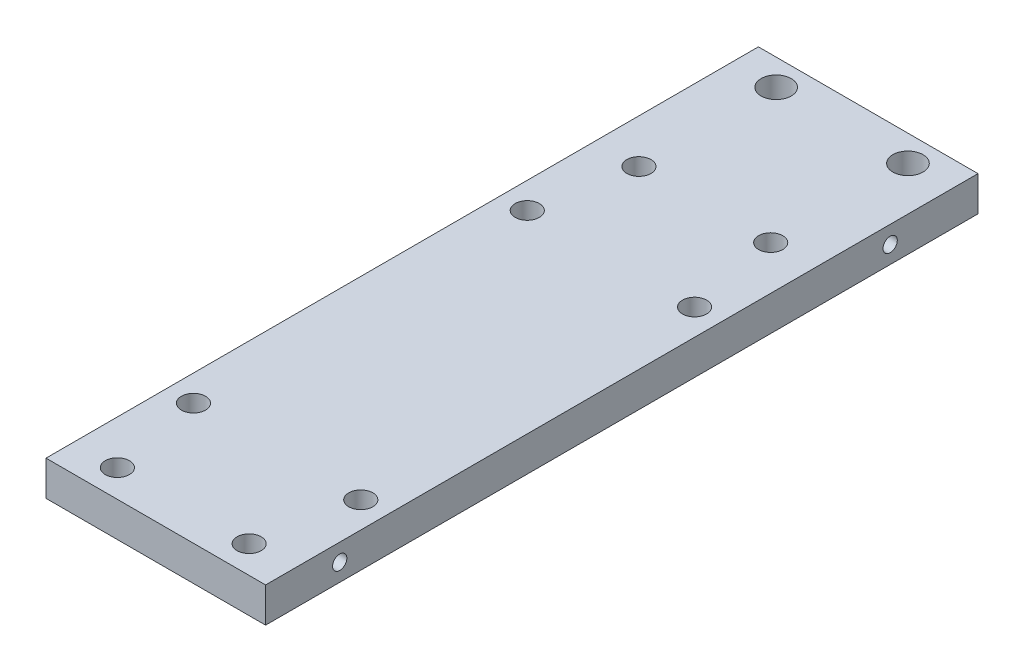
SolidWorks part; units mm, degrees
material "6061 Alloy"
ref_plane "Front Plane" through (0, 0, 0) normal (0, 0, 1) x (1, 0, 0)
ref_plane "Top Plane" through (0, 0, 0) normal (0, 1, 0) x (1, 0, 0)
ref_plane "Right Plane" through (0, 0, 0) normal (1, 0, 0) x (0, 0, -1)
sketch "Sketch1" plane through (0, 0, 0) normal (0, 1, 0) x (1, 0, 0)
  line L1 (-20, 80) -> (20, 80)
  line L2 (-20, 80) -> (-20, -80)
  line L3 (-20, -80) -> (20, -80)
  line L4 (20, 80) -> (20, -80)
  line L5 (0, -80) -> (0, 80) construction
  line L6 (-20, 0) -> (20, 0) construction
  point P0 (0, 0)
  dimension "D1" = 40
  dimension "D2" = 160
extrude "Boss-Extrude1" add sketch "Sketch1" along normal mid plane 6.35
sketch "Sketch3" plane through (0, 0, 0) normal (0, 1, 0) x (1, 0, 0)
  line L0 (0, 75.2375) -> (12, 75.2375) construction
  line L5 (0, -80) -> (0, 80) construction
  line L6 (-20, 0) -> (20, 0) construction
  line L7 (0, 50.2375) -> (12, 50.2375) construction
  line L8 (20, 80) -> (-20, 80) construction
  line L9 (-20, 80) -> (-20, -80) construction
  line L10 (-20, -80) -> (20, -80) construction
  line L11 (20, -80) -> (20, 80) construction
  circle A0 centre (12, 75.2375) radius 2.75
  circle A1 centre (12, 50.2375) radius 2.2
  circle A2 centre (-12, 50.2375) radius 2.2
  circle A3 centre (-12, 75.2375) radius 2.75
  circle A4 centre (-12, -44.7625) radius 2.2
  circle A5 centre (12, -44.7625) radius 2.2
  point P0 (0, 0)
  dimension "D4" = 5.5
  dimension "D5" = 4.4
  dimension "D1" = 4.7625
  dimension "D2" = 25
  dimension "D3" = 12
  dimension "D6" = 2
extrude "M4/5_through" cut sketch "Sketch3" against normal up to surface (3.175 mm away) and the other way blind 6.35 up to face at (0, -3.175, 0)
sketch "Sketch4" plane through (0, 0, -80) normal (0, 0, -1) x (-1, 0, 0)
  circle A0 centre (0, 0) radius 1.35
  dimension "D1" = 2.7
extrude "M3_DRILL" cut sketch "Sketch4" against normal blind 8
sketch "Sketch5" plane through (0, 3.175, 0) normal (0, 1, 0) x (1, 0, 0)
  line L0 (-12, -44.7625) -> (0, -44.7625) construction
  line L2 (0, 0) -> (0, -23.6676) construction
  line L3 (-12, 50.2375) -> (-12, -44.7625) construction
  line L4 (-12, 2.7375) -> (-1.1233, 2.7375) construction
  line L5 (-20, 80) -> (-20, -80) construction
  circle A0 centre (-15.2375, -27.6625) radius 2.2
  circle A1 centre (15.2375, -27.6625) radius 2.2
  circle A2 centre (15.2375, 33.1375) radius 2.2
  circle A3 centre (-15.2375, 33.1375) radius 2.2
  circle A4 centre (-12, -44.7625) radius 2.2 construction
  circle A6 centre (-12, 50.2375) radius 2.2 construction
  dimension "D2" = 4.4
  dimension "D1" = 17.1
  dimension "D3" = 4.7625
extrude "M4_through" cut sketch "Sketch5" against normal up to surface (6.35 mm away) up to face at (12, -3.175, 46.9625)
sketch "Sketch6" plane through (0, 3.175, 0) normal (0, 1, 0) x (1, 0, 0)
  line L0 (-12, -44.7625) -> (12, -44.7625) construction
  line L2 (20, -80) -> (20, 80) construction
  line L3 (-20, -80) -> (20, -80)
  line L4 (-20, -80) -> (-20, -49.7625)
  line L5 (-20, -49.7625) -> (20, -49.7625)
  line L6 (20, -80) -> (20, -49.7625)
  line L7 (0, -49.7625) -> (0, -80) construction
  line L8 (-20, -64.8812) -> (20, -64.8812) construction
  point P220 (0, -64.8812)
  dimension "D1" = 5
extrude "Cut-Extrude1" cut sketch "Sketch6" against normal up to surface (6.35 mm away) up to face at (-15.2375, -3.175, -30.9375)
sketch "Sketch7" plane through (-20, 0, 0) normal (-1, 0, 0) x (0, 0, 1)
  line L0 (36.2625, -3.175) -> (36.2625, 3.175) construction
  line L1 (-80, -3.175) -> (49.7625, -3.175) construction
  line L2 (-80, 3.175) -> (49.7625, 3.175) construction
  line L3 (49.7625, -3.175) -> (49.7625, 3.175) construction
  line L4 (-64, -3.175) -> (-64, 3.175) construction
  line L5 (-80, 3.175) -> (-80, -3.175) construction
  circle A0 centre (36.2625, 0) radius 1.3
  circle A1 centre (-64, 0) radius 1.3
  dimension "D2" = 2.6
  dimension "D3" = 2.6
  dimension "D1" = 13.5
  dimension "D4" = 16
extrude "M3_DRILL2" cut sketch "Sketch7" against normal blind 10
mirror "Mirror1" about plane through (0, 0, 0) normal (1, 0, 0) of "M3_DRILL2"
